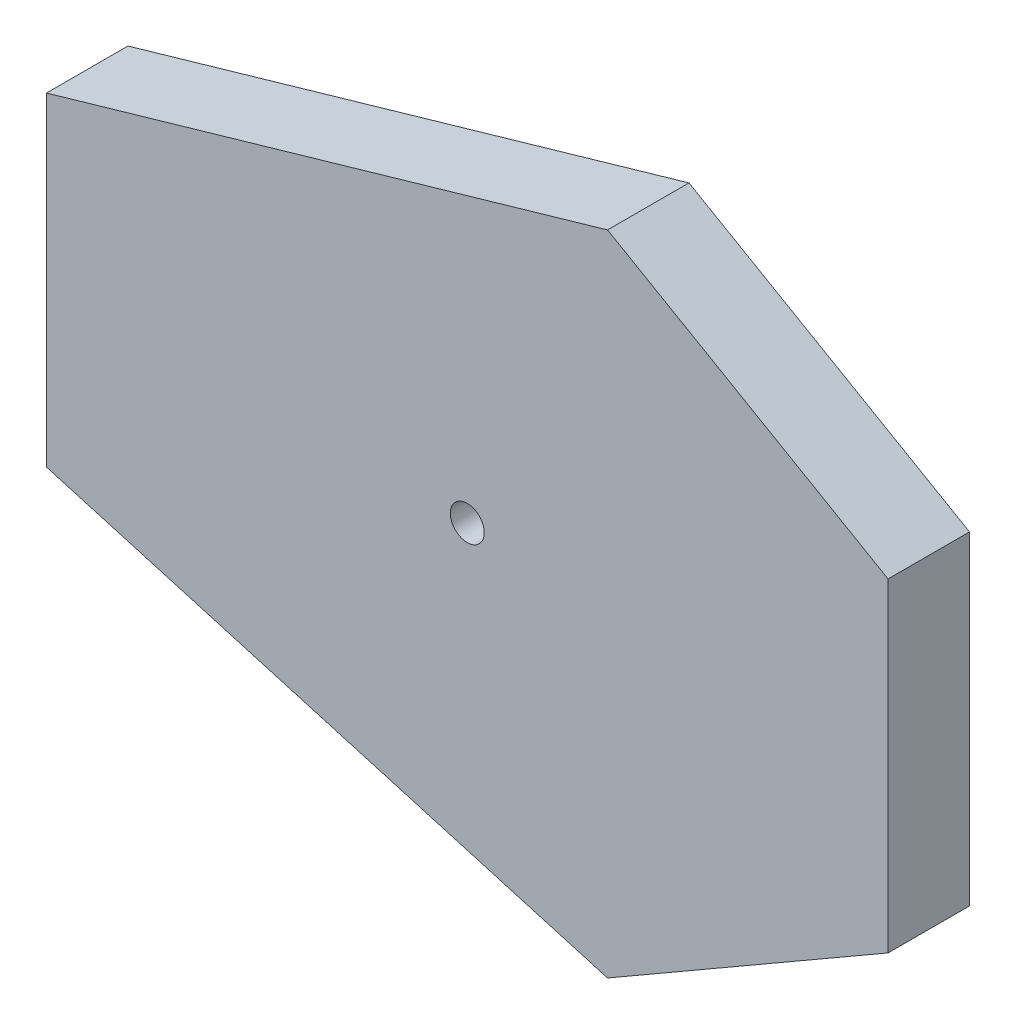
SolidWorks part; units mm, degrees
ref_plane "Front Plane" through (0, 0, 0) normal (0, 0, 1) x (1, 0, 0)
ref_plane "Top Plane" through (0, 0, 0) normal (0, 1, 0) x (1, 0, 0)
ref_plane "Right Plane" through (0, 0, 0) normal (1, 0, 0) x (0, 0, -1)
sketch "Sketch1" plane through (0, 0, 0) normal (0, 0, 1) x (1, 0, 0)
  line L0 (-36.15, 11.9319) -> (-36.15, -11.9319) construction
  line L1 (5.1833, -23.8638) -> (-36.15, -11.9319) construction
  line L2 (5.1833, -23.8638) -> (25.85, -11.9319) construction
  line L3 (25.85, -11.9319) -> (25.85, 11.9319) construction
  line L4 (25.85, 11.9319) -> (5.1833, 23.8638) construction
  line L5 (-36.15, 11.9319) -> (5.1833, 23.8638) construction
  line L6 (-36.15, 11.9319) -> (-36.15, -11.9319)
  line L7 (5.1833, -23.8638) -> (-36.15, -11.9319)
  line L8 (5.1833, -23.8638) -> (25.85, -11.9319)
  line L9 (25.85, -11.9319) -> (25.85, 11.9319)
  line L10 (25.85, 11.9319) -> (5.1833, 23.8638)
  line L11 (-36.15, 11.9319) -> (5.1833, 23.8638)
  circle A0 centre (-5.15, 0) radius 1.25
  dimension "D1" = 2.5
extrude "Boss-Extrude1" add sketch "Sketch1" along normal blind 6
sketch "Sketch2" plane through (0, 0, 0) normal (0, 0, -1) x (-1, 0, 0)
  arc A1 (5.8221, -1.9895) -> (5.8221, 1.9895) centre (5.15, 0) ccw construction
  circle A2 centre (5.15, 0) radius 2.1
extrude "Cut-Extrude1" cut sketch "Sketch2" against normal blind 3
